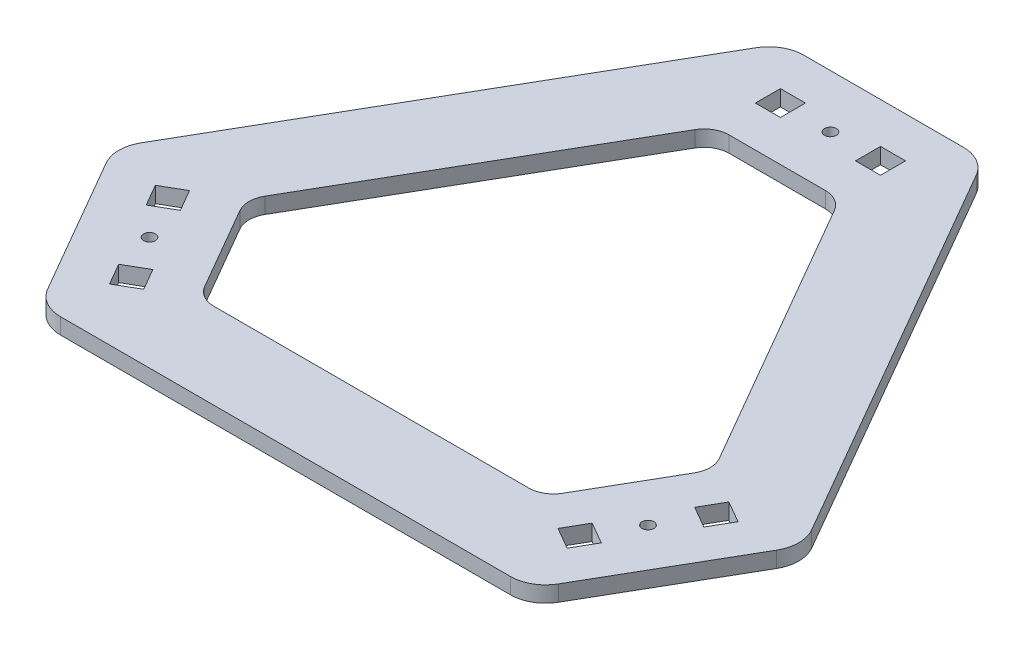
SolidWorks part; units mm, degrees
ref_plane "Front Plane" through (0, 0, 0) normal (0, 0, 1) x (1, 0, 0)
ref_plane "Top Plane" through (0, 0, 0) normal (0, 1, 0) x (1, 0, 0)
ref_plane "Right Plane" through (0, 0, 0) normal (1, 0, 0) x (0, 0, -1)
sketch "Sketch1" plane through (0, 0, 0) normal (0, 1, 0) x (1, 0, 0)
  line L0 (-25.4, 86.5186) -> (25.4, 86.5186)
  line L1 (25.4, 86.5186) -> (87.6273, -21.2623)
  line L2 (87.6273, -21.2623) -> (62.2273, -65.2563)
  line L3 (62.2273, -65.2563) -> (-62.2273, -65.2563)
  line L4 (-62.2273, -65.2563) -> (-87.6273, -21.2623)
  line L5 (-87.6273, -21.2623) -> (-25.4, 86.5186)
  line L6 (-15.875, 59.5141) -> (15.875, 59.5141)
  line L7 (15.875, 59.5141) -> (59.4782, -16.0089)
  line L8 (59.4782, -16.0089) -> (43.6032, -43.5052)
  line L9 (43.6032, -43.5052) -> (-43.6032, -43.5052)
  line L10 (-43.6032, -43.5052) -> (-59.4782, -16.0089)
  line L11 (-59.4782, -16.0089) -> (-15.875, 59.5141)
  circle A0 centre (0, 0) radius 90.17 construction
  circle A1 centre (0, 0) radius 61.595 construction
  dimension "D2" = 180.34
  dimension "D3" = 123.19
  dimension "D1" = 50.8
  dimension "D4" = 31.75
extrude "Boss-Extrude1" add sketch "Sketch1" along normal blind 4.0386
sketch "Sketch2" plane through (0, 4.0386, 0) normal (0, 1, 0) x (1, 0, 0)
  line L0 (9.525, 76.2) -> (15.875, 76.2)
  line L1 (-15.875, 76.2) -> (-9.525, 76.2)
  line L2 (-15.875, 76.2) -> (-15.875, 69.85)
  line L3 (-15.875, 69.85) -> (-9.525, 69.85)
  line L4 (15.875, 76.2) -> (15.875, 69.85)
  line L5 (-9.525, 69.85) -> (9.525, 69.85) construction
  line L6 (-9.525, 76.2) -> (-9.525, 69.85)
  line L7 (0, 69.85) -> (0, 0) construction
  line L8 (9.525, 76.2) -> (9.525, 69.85)
  line L9 (9.525, 69.85) -> (15.875, 69.85)
  line L10 (-9.525, 73.025) -> (9.525, 73.025) construction
  circle A0 centre (0, 73.025) radius 1.5
  dimension "D5" = 3
  dimension "D1" = 69.85
  dimension "D2" = 6.35
  dimension "D3" = 6.35
  dimension "D4" = 19.05
extrude "Cut-Extrude1" cut sketch "Sketch2" against normal through all
ref_axis "Axis1" through (0, 2.3285, 0) along (0, 1, 0)
pattern_circular "CirPattern1" count 3 every 120 about axis through (0, 2.3285, 0) along (0, 1, 0) of "Cut-Extrude1"
fillet "Fillet1" radius 8.89 6 edges at (-25.4, 2.0193, -86.5186) (25.4, 2.0193, -86.5186) (87.6273, 2.0193, 21.2623) (62.2273, 2.0193, 65.2563) (-87.6273, 2.0193, 21.2623) (-62.2273, 2.0193, 65.2563)
fillet "Fillet2" radius 6.35 6 edges at (15.875, 2.0193, -59.5141) (-15.875, 2.0193, -59.5141) (-59.4782, 2.0193, 16.0089) (-43.6032, 2.0193, 43.5052) (59.4782, 2.0193, 16.0089) (43.6032, 2.0193, 43.5052)
